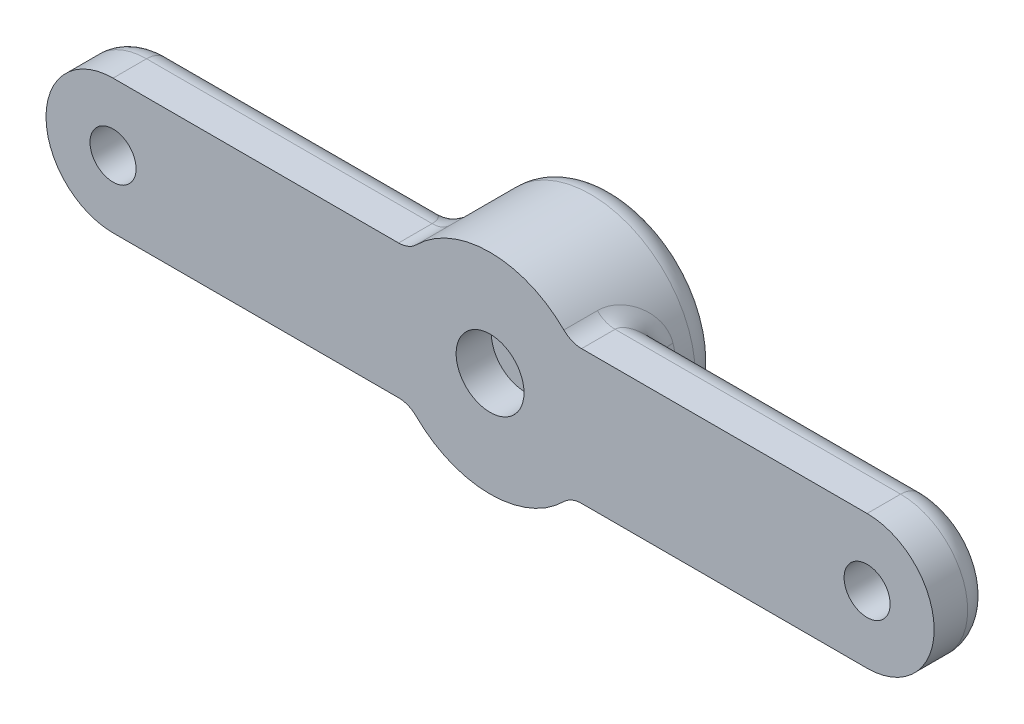
SolidWorks part; units mm, degrees
ref_plane "Front Plane" through (0, 0, 0) normal (0, 0, 1) x (1, 0, 0)
ref_plane "Top Plane" through (0, 0, 0) normal (0, 1, 0) x (1, 0, 0)
ref_plane "Right Plane" through (0, 0, 0) normal (1, 0, 0) x (0, 0, -1)
sketch "Sketch1" plane through (0, 0, 0) normal (0, 0, 1) x (1, 0, 0)
  line L0 (45, 0) -> (-45, 0) construction
  line L1 (45, -8) -> (-45, -8)
  line L2 (45, 8) -> (-45, 8)
  arc A0 (45, -8) -> (45, 8) centre (45, 0) ccw
  arc A1 (-45, 8) -> (-45, -8) centre (-45, 0) ccw
  circle A2 centre (-45, 0) radius 2.75
  circle A3 centre (45, 0) radius 2.75
  circle A4 centre (0, 0) radius 1.75
  point P2 (0, 0)
  dimension "D1" = 5.5
  dimension "D3" = 8
  dimension "D4" = 3.5
  dimension "D2" = 90
extrude "Boss-Extrude1" add sketch "Sketch1" along normal blind 7
sketch "Sketch2" plane through (0, 0, 7) normal (0, 0, 1) x (1, 0, 0)
  circle A0 centre (0, 0) radius 12.5
  circle A1 centre (0, 0) radius 1.75
  circle A2 centre (0, 0) radius 1.75 construction
  dimension "D1" = 25
extrude "Boss-Extrude2" add sketch "Sketch2" against normal blind 15
sketch "Sketch3" plane through (0, 0, 7) normal (0, 0, 1) x (1, 0, 0)
  circle A0 centre (0, 0) radius 4.05
  dimension "D1" = 8.1
extrude "Cut-Extrude1" cut sketch "Sketch3" against normal blind 4.2
fillet "Fillet1" radius 3 13 edges at (9.6047, 8, 3.5) (9.6047, -8, 3.5) (-9.6047, -8, 3.5) (-9.6047, 8, 3.5) (53, 0, 0) (27.3023, 8, 0) (12.5, 0, 0) (27.3023, -8, 0) (-53, 0, 0) (-27.3023, -8, 0) (-12.5, 0, 0) (-27.3023, 8, 0) (12.5, 0, -8)
